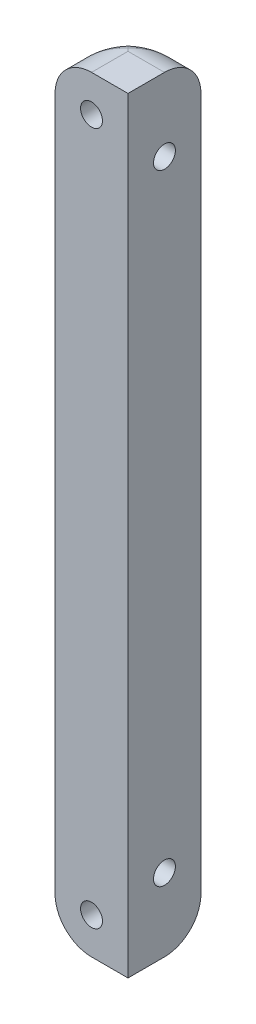
SolidWorks part; units mm, degrees
ref_plane "Front Plane" through (0, 0, 0) normal (0, 0, 1) x (1, 0, 0)
ref_plane "Top Plane" through (0, 0, 0) normal (0, 1, 0) x (1, 0, 0)
ref_plane "Right Plane" through (0, 0, 0) normal (1, 0, 0) x (0, 0, -1)
sketch "Sketch1" plane through (0, 0, 0) normal (0, 1, 0) x (1, 0, 0)
  line L1 (-6.35, -6.35) -> (6.35, -6.35)
  line L2 (-6.35, -6.35) -> (-6.35, 6.35)
  line L3 (-6.35, 6.35) -> (6.35, 6.35)
  line L4 (6.35, -6.35) -> (6.35, 6.35)
  line L5 (-6.35, -6.35) -> (6.35, 6.35) construction
  line L6 (-6.35, 6.35) -> (6.35, -6.35) construction
  point P0 (0, 0)
  dimension "D1" = 12.7
  dimension "D2" = 12.7
extrude "Boss-Extrude1" add sketch "Sketch1" along normal blind 133.35
sketch "Sketch2" plane through (0, 0, 6.35) normal (0, 0, 1) x (1, 0, 0)
  line L0 (-6.35, 0) -> (6.35, 0) construction
  line L1 (-6.35, 133.35) -> (6.35, 133.35) construction
  circle A0 centre (0, 6.35) radius 1.905
  circle A1 centre (0, 127) radius 1.905
  dimension "D1" = 3.81
  dimension "D2" = 6.35
  dimension "D3" = 6.35
extrude "Cut-Extrude1" cut sketch "Sketch2" against normal through all
sketch "Sketch3" plane through (6.35, 0, 0) normal (1, 0, 0) x (0, 0, -1)
  line L0 (-6.35, 0) -> (6.35, 0) construction
  line L1 (-6.35, 133.35) -> (6.35, 133.35) construction
  circle A0 centre (0, 120.65) radius 1.905
  circle A1 centre (0, 12.7) radius 1.905
  dimension "D3" = 3.81
  dimension "D1" = 12.7
  dimension "D2" = 12.7
extrude "Cut-Extrude2" cut sketch "Sketch3" against normal through all
chamfer "Chamfer1" distance 9.525 angle 45 1 edges at (-6.35, 66.675, -6.35)
fillet "Fillet1" radius 6.35 4 edges at (4.7625, 0, -6.35) (-6.35, 0, 4.7625) (4.7625, 133.35, -6.35) (-6.35, 133.35, 4.7625)
fillet "Fillet2" radius 1.5875 6 edges at (-5.0201, 130.8886, 1.8451) (-5.0201, 2.4614, 1.8451) (-6.35, 66.675, 3.175) (1.8451, 2.4614, -5.0201) (1.8451, 130.8886, -5.0201) (3.175, 66.675, -6.35)
